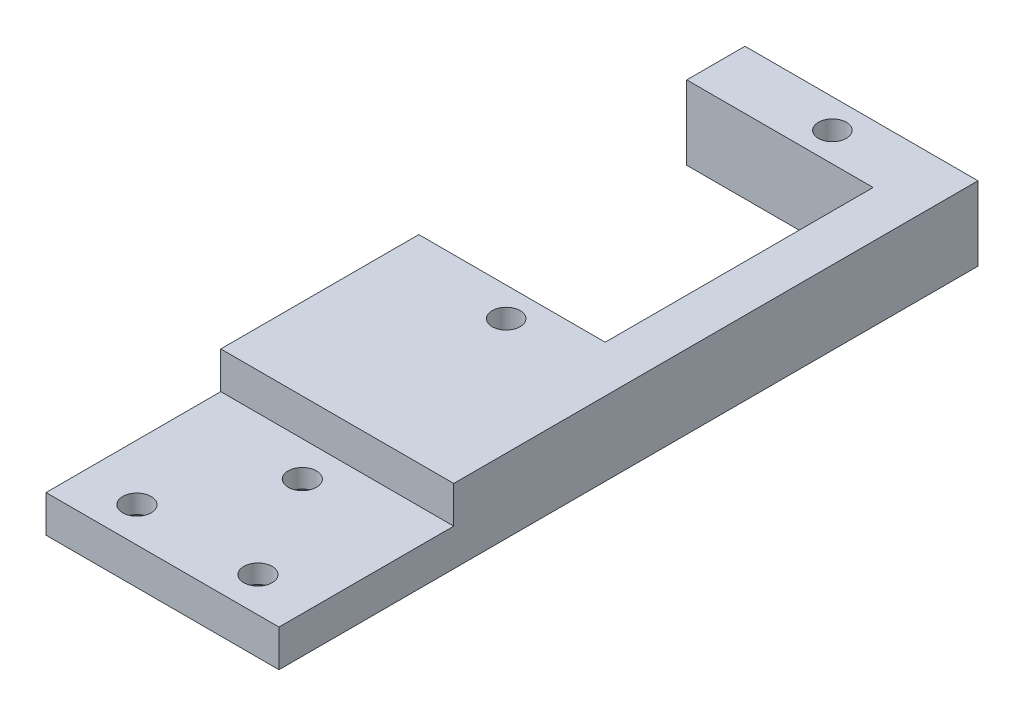
SolidWorks part; units mm, degrees
material "ABS"
ref_plane "Front" through (0, 0, 0) normal (0, 0, 1) x (1, 0, 0)
ref_plane "Top" through (0, 0, 0) normal (0, 1, 0) x (1, 0, 0)
ref_plane "Right" through (0, 0, 0) normal (1, 0, 0) x (0, 0, -1)
sketch "Sketch2" plane through (0, 0, 0) normal (0, 1, 0) x (1, 0, 0)
  line L1 (0, 0) -> (20, 0)
  line L2 (0, 0) -> (0, -60)
  line L3 (0, -60) -> (20, -60)
  line L4 (20, 0) -> (20, -60)
  dimension "D1" = 20
  dimension "D2" = 60
extrude "Boss-Extrude1" add sketch "Sketch2" along normal blind 6.35
sketch "Sketch4" plane through (0, 6.35, 0) normal (0, 1, 0) x (1, 0, 0)
  line L0 (0, 0) -> (0, -60) construction
  line L1 (0, -5) -> (16, -5)
  line L2 (0, -5) -> (0, -28)
  line L3 (0, -28) -> (16, -28)
  line L4 (16, -5) -> (16, -28)
  line L5 (20, -60) -> (20, 0) construction
  line L6 (20, 0) -> (0, 0) construction
  dimension "D1" = 4
  dimension "D2" = 5
  dimension "D3" = 23
extrude "Cut-Extrude1" cut sketch "Sketch4" against normal through all
hole_wizard "M2 Clearance Hole1" positions "Sketch8" profile "Sketch9" hole size "M2" standard "IS" end condition through all
sketch "Sketch8" plane through (0, 6.35, 0) normal (0, 1, 0) x (1, 0, 0)
  line L0 (10, 0) -> (10, -60) construction
  line L1 (20, 0) -> (0, 0) construction
  line L2 (0, -60) -> (20, -60) construction
  line L3 (0, -28) -> (16, -28) construction
  point P9 (10, -2.5)
  point P11 (10, -30.5)
  dimension "D1" = 2.5
  dimension "D2" = 2.5
sketch "Sketch9" plane through (10, 6.35, 30.5) normal (1, 0, 0) x (0, 0, 1)
  line L0 (0, 0) -> (0, 6.35)
  line L1 (0, 6.35) -> (1.2, 6.35)
  line L2 (1.2, 6.35) -> (1.2, 0)
  line L5 (1.2, 0) -> (0, 0)
  line L11 (0, -6.35) -> (0, 107.95) construction
  dimension "Thru Hole Dia." = 2.4
  dimension "Thru Hole Depth" = 6.35
sketch "Sketch10" plane through (20, 0, 0) normal (1, 0, 0) x (0, 0, -1)
  line L0 (-60, 6.35) -> (-60, 0) construction
  line L1 (-60, 6.35) -> (-45, 6.35)
  line L2 (-60, 6.35) -> (-60, 3.175)
  line L3 (-60, 3.175) -> (-45, 3.175)
  line L4 (-45, 6.35) -> (-45, 3.175)
  dimension "D1" = 15
extrude "Cut-Extrude2" cut sketch "Sketch10" against normal through all
sketch "Sketch12" plane through (0, 3.175, 0) normal (0, 1, 0) x (1, 0, 0)
  line L0 (10, -60) -> (10, -45) construction
  line L1 (0, -60) -> (20, -60) construction
  line L2 (0, -45) -> (20, -45) construction
  line L3 (10, -48) -> (15.1962, -57) construction
  line L4 (15.1962, -57) -> (4.8038, -57) construction
  line L5 (4.8038, -57) -> (10, -48) construction
  dimension "D1" = 9
  dimension "D2" = 3
hole_wizard "#2 Clearance Hole1" positions "Sketch13" profile "Sketch14" hole size "#2" standard "ANSI Inch" end condition through all
sketch "Sketch13" plane through (0, 3.175, 0) normal (0, 1, 0) x (1, 0, 0)
  point P0 (10, -48)
  point P3 (4.8038, -57)
  point P6 (15.1962, -57)
sketch "Sketch14" plane through (10, 3.175, 48) normal (1, 0, 0) x (0, 0, 1)
  line L0 (0, 0) -> (0, 3.175)
  line L1 (0, 3.175) -> (2.54, 3.175)
  line L2 (1.2192, 1.6009) -> (1.2192, 0)
  line L5 (1.2192, 0) -> (0, 0)
  line L7 (2.54, 3.175) -> (1.2192, 1.6009)
  line L8 (-2.54, 3.175) -> (-1.2192, 1.6009) construction
  line L11 (0, -6.35) -> (0, 107.95) construction
  dimension "Thru Hole Dia." = 2.4384
  dimension "Thru Hole Depth" = 3.175
  dimension "Far C'Sink Dia." = 5.08
  dimension "Far C'Sink Angle" = 80
